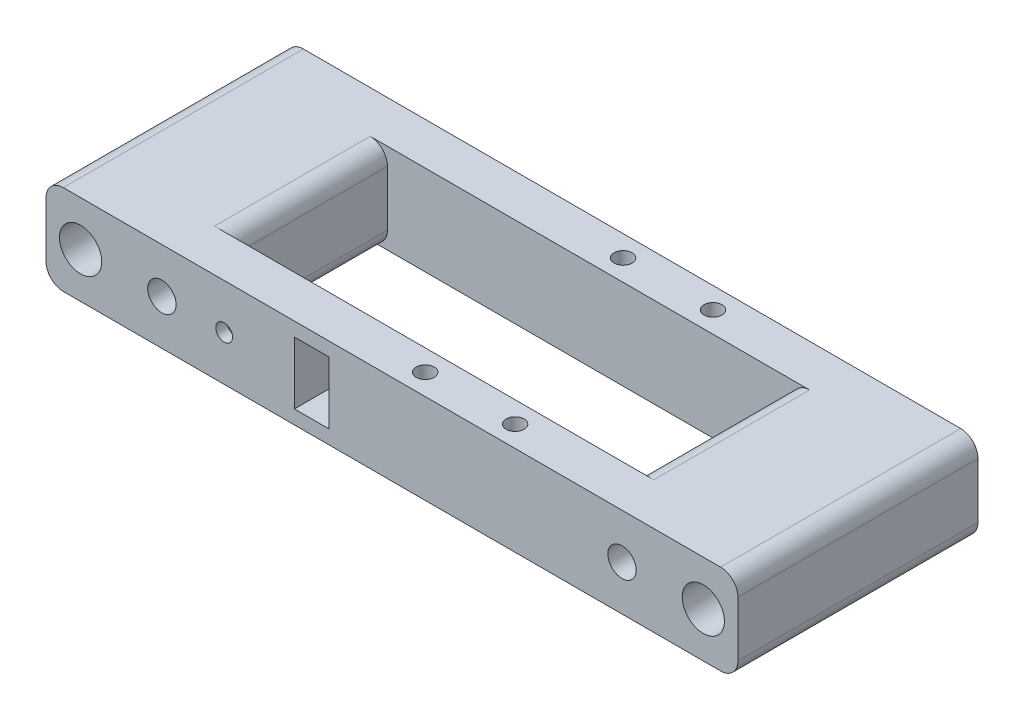
SolidWorks part; units mm, degrees
ref_plane "Front Plane" through (0, 0, 0) normal (0, 0, 1) x (1, 0, 0)
ref_plane "Top Plane" through (0, 0, 0) normal (0, 1, 0) x (1, 0, 0)
ref_plane "Right Plane" through (0, 0, 0) normal (1, 0, 0) x (0, 0, -1)
sketch "Sketch1" plane through (0, 0, 0) normal (0, 0, 1) x (1, 0, 0)
  line L0 (-58.5, 26) -> (-58.5, 0) construction
  line L1 (0, 0) -> (-100, 0)
  line L2 (0, 0) -> (0, 26)
  line L3 (0, 26) -> (-100, 26)
  line L4 (-100, 0) -> (-100, 26)
  circle A0 centre (-90, 13) radius 6.1
  circle A1 centre (-66.5, 13) radius 4.1
  point P9 (-100, 13)
  dimension "D3" = 12.2
  dimension "D4" = 8.2
  dimension "D1" = 100
  dimension "D2" = 26
  dimension "D5" = 23.5
  dimension "D6" = 10
  dimension "D7" = 8
  dimension "D8" = 41.5
extrude "Boss-Extrude1" add sketch "Sketch1" along normal blind 40
sketch "Sketch2" plane through (0, 0, 0) normal (0, 0, -1) x (-1, 0, 0)
  line L1 (100, 26) -> (0, 26)
  line L2 (100, 26) -> (100, 0)
  line L3 (100, 0) -> (0, 0)
  line L4 (0, 26) -> (0, 0)
extrude "Boss-Extrude2" add sketch "Sketch2" along normal blind 29.4
sketch "Sketch3" plane through (0, 26, 0) normal (0, 1, 0) x (1, 0, 0)
  line L0 (0, -40) -> (0, 29.4) construction
  line L1 (0, 17.2) -> (-58.5, 17.2)
  line L2 (0, 17.2) -> (0, -27.8)
  line L3 (0, -27.8) -> (-58.5, -27.8)
  line L4 (-58.5, 17.2) -> (-58.5, -27.8)
  line L5 (-100, -40) -> (-100, 29.4) construction
  line L6 (-100, 29.4) -> (0, 29.4) construction
  line L7 (0, -40) -> (-100, -40) construction
  dimension "D1" = 41.5
  dimension "D2" = 12.2
  dimension "D3" = 12.2
extrude "Cut-Extrude1" cut sketch "Sketch3" against normal up to next
mirror "Mirror2" about plane through (0, 0, 40) normal (-1, 0, 0) of "Boss-Extrude2", "Cut-Extrude1", "Boss-Extrude1"
sketch "Sketch4" plane through (0, 26, 0) normal (0, 1, 0) x (1, 0, 0)
  line L0 (-100, 29.4) -> (100, 29.4) construction
  line L1 (-5.5, 29.4) -> (-5.5, 17.2) construction
  line L2 (58.5, 17.2) -> (-58.5, 17.2) construction
  line L3 (58.5, 17.2) -> (58.5, -27.8) construction
  circle A0 centre (3.5, 23.3) radius 2.6
  circle A1 centre (29.5, 23.3) radius 2.6
  dimension "D1" = 6.1
  dimension "D3" = 9
  dimension "D4" = 26
  dimension "D5" = 5.2
  dimension "D2" = 64
extrude "Cut-Extrude2" cut sketch "Sketch4" against normal through all
sketch "Sketch5" plane through (0, 0, 0) normal (0, -1, 0) x (1, 0, 0)
  line L1 (34.2343, -23.3) -> (31.8671, -19.2)
  line L2 (31.8671, -19.2) -> (27.1329, -19.2)
  line L3 (27.1329, -19.2) -> (24.7657, -23.3)
  line L4 (24.7657, -23.3) -> (27.1329, -27.4)
  line L5 (27.1329, -27.4) -> (31.8671, -27.4)
  line L6 (31.8671, -27.4) -> (34.2343, -23.3)
  line L7 (-1.2343, -23.3) -> (1.1329, -27.4)
  line L8 (1.1329, -27.4) -> (5.8671, -27.4)
  line L9 (5.8671, -27.4) -> (8.2343, -23.3)
  line L10 (8.2343, -23.3) -> (5.8671, -19.2)
  line L11 (5.8671, -19.2) -> (1.1329, -19.2)
  line L12 (1.1329, -19.2) -> (-1.2343, -23.3)
  circle A0 centre (29.5, -23.3) radius 4.1 construction
  circle A1 centre (3.5, -23.3) radius 4.1 construction
  dimension "D1" = 8.2
  dimension "D2" = 8.2
extrude "Cut-Extrude3" cut sketch "Sketch5" against normal blind 4
ref_plane "Plane1" through (0, 0, 5.3) normal (0, 0, 1) x (1, 0, 0)
mirror "Mirror3" about plane through (0, 0, 5.3) normal (0, 0, 1) of "Cut-Extrude3", "Cut-Extrude2"
sketch "Sketch6" plane through (0, 0, 40) normal (0, 0, 1) x (1, 0, 0)
  line L0 (-8.1, 26) -> (-8.1, 0) construction
  line L1 (100, 26) -> (-100, 26) construction
  line L2 (-100, 0) -> (100, 0) construction
  line L3 (0.9, 26) -> (0.9, 4) construction
  line L4 (-100, 26) -> (-100, 0) construction
  line L5 (-18.2, 22) -> (-28.2, 22)
  line L6 (-18.2, 22) -> (-18.2, 4)
  line L7 (-18.2, 4) -> (-28.2, 4)
  line L8 (-28.2, 22) -> (-28.2, 4)
  point P12 (-28.2, 13)
  point P15 (-100, 13)
  dimension "D1" = 9
  dimension "D2" = 10.1
  dimension "D3" = 10
  dimension "D4" = 18
extrude "Cut-Extrude4" cut sketch "Sketch6" against normal up to vertex (14 mm away) up to point (0, -58.5, 26)
fillet "Fillet1" radius 5 8 edges at (58.5, 0, 5.3) (-58.5, 0, 5.3) (58.5, 26, 5.3) (100, 0, 5.3) (100, 26, 5.3) (-100, 0, 5.3) (-100, 26, 5.3) (-58.5, 26, 5.3)
sketch "Sketch7" plane through (0, 0, 27.8) normal (0, 0, -1) x (-1, 0, 0)
  line L0 (58.5, 5) -> (58.5, 21) construction
  circle A0 centre (48.5, 13) radius 5
  point P4 (58.5, 13)
  dimension "D1" = 10
  dimension "D2" = 10
extrude "Cut-Extrude5" cut sketch "Sketch7" against normal blind 9 contours A0
sketch "Sketch8" plane through (0, 0, 36.8) normal (0, 0, -1) x (-1, 0, 0)
  circle A0 centre (48.5, 13) radius 2.4278
extrude "Cut-Extrude6" cut sketch "Sketch8" against normal up to next
